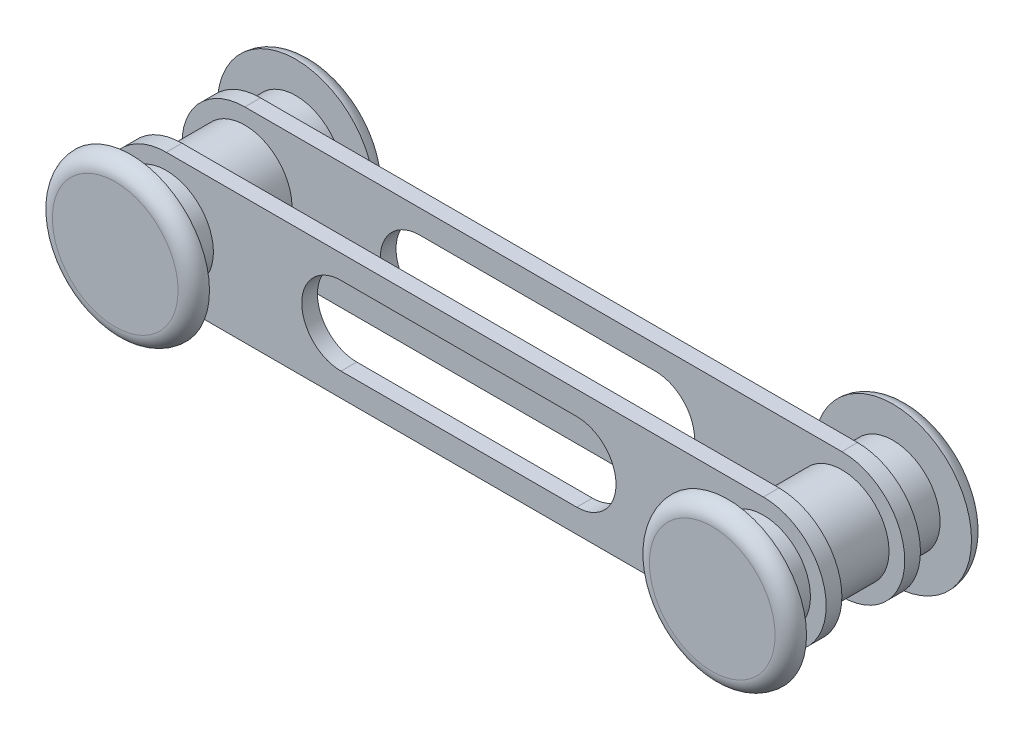
SolidWorks part; units mm, degrees
ref_plane "Front Plane" through (0, 0, 0) normal (0, 0, 1) x (1, 0, 0)
ref_plane "Top Plane" through (0, 0, 0) normal (0, 1, 0) x (1, 0, 0)
ref_plane "Right Plane" through (0, 0, 0) normal (1, 0, 0) x (0, 0, -1)
sketch "Sketch1" plane through (0, 0, 0) normal (0, 0, 1) x (1, 0, 0)
  circle A0 centre (0, 0) radius 30
  dimension "D1" = 60
extrude "Boss-Extrude1" add sketch "Sketch1" along normal mid plane 105
ref_plane "Plane1" through (0, 0, 30) normal (0, 0, 1) x (1, 0, 0)
sketch "Sketch2" plane through (0, 0, 30) normal (0, 0, 1) x (1, 0, 0)
  line L0 (0, 40) -> (0, -40) construction
  line L1 (0, 40) -> (380, 40)
  line L2 (0, 0) -> (380, 0) construction
  line L3 (380, 40) -> (380, -40) construction
  line L4 (0, -40) -> (380, -40)
  arc A0 (0, 40) -> (0, -40) centre (0, 0) ccw
  arc A1 (380, -40) -> (380, 40) centre (380, 0) ccw
  point P6 (0, 0)
  dimension "D1" = 40
  dimension "D2" = 380
extrude "Boss-Extrude2" add sketch "Sketch2" against normal blind 10
sketch "Sketch3" plane through (0, 0, 30) normal (0, 0, 1) x (1, 0, 0)
  line L0 (111.2324, 0) -> (261.2324, 0) construction
  line L1 (111.2324, 25) -> (261.2324, 25)
  line L2 (111.2324, -25) -> (261.2324, -25)
  arc A0 (111.2324, 25) -> (111.2324, -25) centre (111.2324, 0) ccw
  arc A1 (261.2324, -25) -> (261.2324, 25) centre (261.2324, 0) ccw
  point P2 (186.2324, 0)
  dimension "D2" = 25
  dimension "D1" = 150
extrude "Cut-Extrude1" cut sketch "Sketch3" against normal through all
sketch "Sketch4" plane through (0, 0, 0) normal (0, 0, 1) x (1, 0, 0)
  circle A0 centre (380, 0) radius 30
  dimension "D1" = 60
extrude "Boss-Extrude3" add sketch "Sketch4" along normal mid plane 105
mirror "Mirror1" about plane through (0, 0, 0) normal (0, 0, 1) of "Cut-Extrude1", "Boss-Extrude2"
sketch "Sketch5" plane through (0, 0, 52.5) normal (0, 0, 1) x (1, 0, 0)
  circle A0 centre (0, 0) radius 50
  circle A1 centre (380, 0) radius 50
  dimension "D1" = 100
  dimension "D2" = 100
extrude "Boss-Extrude4" add sketch "Sketch5" along normal blind 10
fillet "Fillet1" radius 10 2 edges at (430, 0, 62.5) (50, 0, 62.5)
mirror "Mirror2" about plane through (0, 0, 0) normal (0, 0, 1) of "Boss-Extrude4", "Fillet1"
